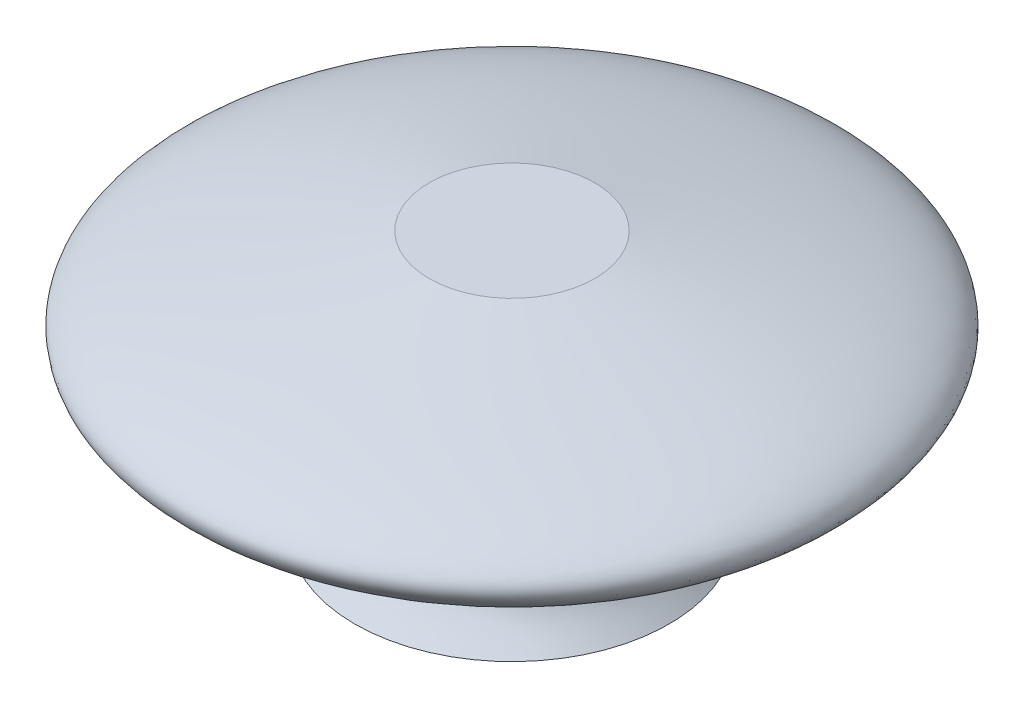
SolidWorks part; units mm, degrees
ref_plane "Front Plane" through (0, 0, 0) normal (1, 0, 0) x (0, 1, 0)
ref_plane "Top Plane" through (0, 0, 0) normal (0, 0, 1) x (0, 1, 0)
ref_plane "Right Plane" through (0, 0, 0) normal (0, 1, 0) x (-1, 0, 0)
sketch "Sketch1" plane through (0, 0, 0) normal (1, 0, 0) x (0, 1, 0)
  line L0 (0, 76.2) -> (0, 0)
  line L1 (127, 40.1749) -> (127, 0)
  line L2 (127, 0) -> (0, 0)
  spline S0 degree 4 poles (-12.6998, 87.3453) (-12.4772, 87.2031) (-12.0347, 86.9137) (-11.1598, 86.3131) (-9.8912, 85.3706) (-8.4394, 84.1976) (-7.058, 83.0004) (-5.8552, 81.9046) (-4.7513, 80.8752) (-3.4789, 79.6498) (-2.4153, 78.6114) (-0.473, 76.6743) (0.4928, 75.7058) (2.2466, 73.9568) (3.1881, 73.0351) (4.2434, 72.0123) (4.9968, 71.297) (5.7917, 70.5546) (6.5876, 69.8287) (7.5953, 68.9335) (9.2372, 67.5349) (11.3676, 65.8761) (14.088, 64.1003) (17.053, 62.7339) (19.7009, 62.0321) (22.5472, 61.8421) (25.1919, 62.2683) (27.7355, 63.3008) (30.5226, 65.0655) (33.157, 67.3578) (35.8606, 70.377) (38.5917, 74.0989) (41.1032, 78.0557) (43.4558, 82.1931) (45.7294, 86.5439) (47.9486, 91.0907) (50.1346, 95.8196) (52.3072, 100.7197) (54.4268, 105.6427) (56.5137, 110.5797) (58.5865, 115.5226) (60.6631, 120.4639) (62.7626, 125.3956) (64.9062, 130.3083) (66.8433, 134.5798) (68.569, 138.2108) (70.0654, 141.2082) (71.3055, 143.584) (72.9186, 146.5167) (74.639, 149.3856) (76.5037, 152.1644) (78.5262, 154.6956) (80.2218, 156.49) (82.1097, 158.0709) (84.1002, 159.2355) (86.0845, 159.7867) (87.8593, 159.7363) (89.7733, 159.2523) (91.4828, 158.2958) (93.0877, 156.9247) (94.9195, 154.8739) (96.7317, 152.3505) (98.6726, 149.0132) (100.6794, 144.861) (102.5674, 140.3457) (104.3754, 135.5034) (106.1204, 130.3483) (107.8176, 124.8871) (109.4786, 119.131) (111.4388, 111.8991) (113.6385, 103.1878) (116.0437, 92.9743) (118.6312, 81.2805) (121.1078, 69.5492) (123.2082, 59.2535) (124.94, 50.6008) (126.9851, 40.264) (128.1708, 34.2149) (130.8452, 20.5825) (131.3994, 17.7643) (132.421, 12.5915) knots 0 0 0 0 0 0.003282 0.006565 0.01313 0.019694 0.026259 0.029542 0.032824 0.039389 0.045954 0.052518 0.059209 0.065899 0.069244 0.072589 0.075934 0.079279 0.082624 0.085969 0.092659 0.106039 0.116107 0.126175 0.132999 0.139822 0.151319 0.159054 0.166789 0.180638 0.194486 0.209245 0.224005 0.238765 0.253524 0.270151 0.286779 0.303406 0.320033 0.33666 0.353287 0.369914 0.386541 0.403168 0.419796 0.428109 0.436423 0.444736 0.45305 0.469632 0.477924 0.486215 0.493217 0.500219 0.50839 0.514639 0.518323 0.522008 0.532762 0.538589 0.544416 0.55607 0.571247 0.586425 0.601602 0.61678 0.635368 0.653956 0.672545 0.691133 0.72831 0.765486 0.802663 0.83984 0.877016 0.895605 0.914193 0.957097 1 1 1 1 1 construction
  spline S1 degree 4 poles (0, 76.2) (0.3285, 75.8715) (0.9872, 75.2128) (2.2466, 73.9568) (3.1881, 73.0351) (4.2434, 72.0123) (4.9968, 71.297) (5.7917, 70.5546) (6.5876, 69.8287) (7.5953, 68.9335) (9.2372, 67.5349) (11.3676, 65.8761) (14.088, 64.1003) (17.053, 62.7339) (19.7009, 62.0321) (22.5472, 61.8421) (25.1919, 62.2683) (27.7355, 63.3008) (30.5226, 65.0655) (33.157, 67.3578) (35.8606, 70.377) (38.5917, 74.0989) (41.1032, 78.0557) (43.4558, 82.1931) (45.7294, 86.5439) (47.9486, 91.0907) (50.1346, 95.8196) (52.3072, 100.7197) (54.4268, 105.6427) (56.5137, 110.5797) (58.5865, 115.5226) (60.6631, 120.4639) (62.7626, 125.3956) (64.9062, 130.3083) (66.8433, 134.5798) (68.569, 138.2108) (70.0654, 141.2082) (71.3055, 143.584) (72.9186, 146.5167) (74.639, 149.3856) (76.5037, 152.1644) (78.5262, 154.6956) (80.2218, 156.49) (82.1097, 158.0709) (84.1002, 159.2355) (86.0845, 159.7867) (87.8593, 159.7363) (89.7733, 159.2523) (91.4828, 158.2958) (93.0877, 156.9247) (94.9195, 154.8739) (96.7317, 152.3505) (98.6726, 149.0132) (100.6794, 144.861) (102.5674, 140.3457) (104.3754, 135.5034) (106.1204, 130.3483) (107.8176, 124.8871) (109.4786, 119.131) (111.4388, 111.8991) (113.6385, 103.1878) (116.0437, 92.9743) (118.6312, 81.2805) (121.1078, 69.5492) (123.2082, 59.2535) (124.94, 50.6008) (126.2368, 44.0461) (126.7506, 41.4414) (127, 40.1749) knots 0.052518 0.052518 0.052518 0.052518 0.052518 0.059209 0.065899 0.069244 0.072589 0.075934 0.079279 0.082624 0.085969 0.092659 0.106039 0.116107 0.126175 0.132999 0.139822 0.151319 0.159054 0.166789 0.180638 0.194486 0.209245 0.224005 0.238765 0.253524 0.270151 0.286779 0.303406 0.320033 0.33666 0.353287 0.369914 0.386541 0.403168 0.419796 0.428109 0.436423 0.444736 0.45305 0.469632 0.477924 0.486215 0.493217 0.500219 0.50839 0.514639 0.518323 0.522008 0.532762 0.538589 0.544416 0.55607 0.571247 0.586425 0.601602 0.61678 0.635368 0.653956 0.672545 0.691133 0.72831 0.765486 0.802663 0.83984 0.877016 0.895605 0.914193 0.914193 0.914193 0.914193 0.914193
  point P2 (-122.5744, 141.3724)
  point P3 (0, 0)
  point P9 (0, 0)
  dimension "D1" = 76.2
  dimension "D2" = 127
revolve "Revolve1" add sketch "Sketch1" angle 360 about L2
shell "Shell4" thickness 6.35 removed face at (0, 0, 76.2)
